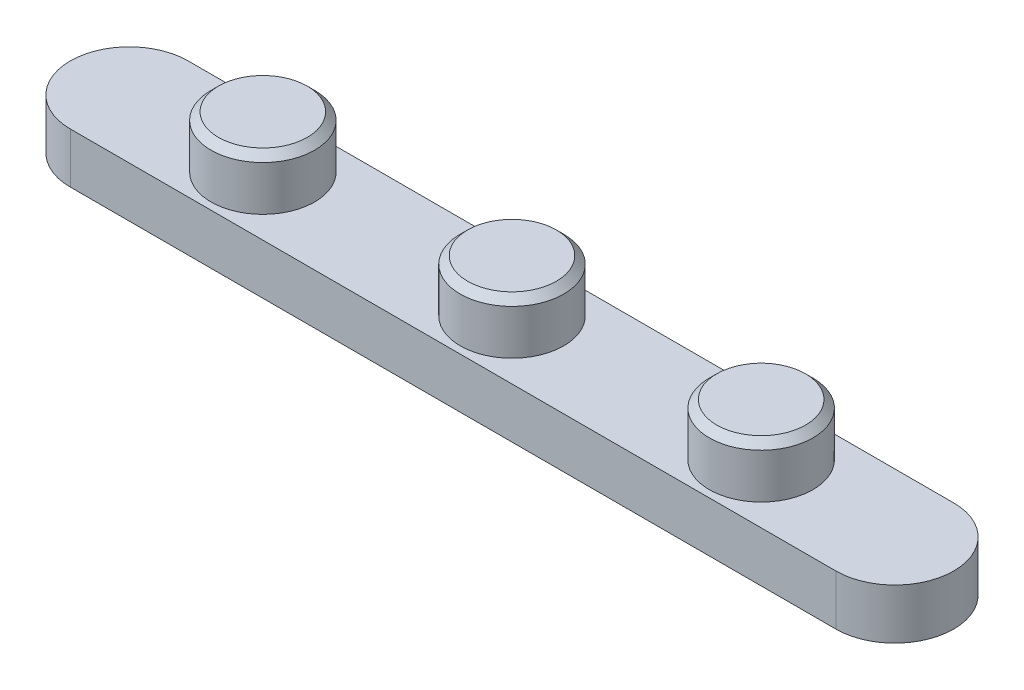
SolidWorks part; units mm, degrees
material "Plain Carbon Steel"
ref_plane "Front Plane" through (0, 0, 0) normal (0, 0, 1) x (1, 0, 0)
ref_plane "Top Plane" through (0, 0, 0) normal (0, 1, 0) x (1, 0, 0)
ref_plane "Right Plane" through (0, 0, 0) normal (1, 0, 0) x (0, 0, -1)
sketch "Sketch1" plane through (0, 0, 0) normal (0, 1, 0) x (1, 0, 0)
  line L0 (-25.855, 0) -> (25.855, 0) construction
  line L1 (-25.855, 3.98) -> (25.855, 3.98)
  line L2 (-25.855, -3.98) -> (25.855, -3.98)
  line L3 (0, 0) -> (0, 65.4823) construction
  arc A0 (-25.855, 3.98) -> (-25.855, -3.98) centre (-25.855, 0) ccw
  arc A1 (25.855, -3.98) -> (25.855, 3.98) centre (25.855, 0) ccw
  circle A2 centre (-16.8275, 0) radius 3.5
  circle A3 centre (0, 0) radius 3.5
  circle A4 centre (16.8275, 0) radius 3.5
  point P2 (0, 0)
  dimension "D1" = 7
  dimension "D4" = 59.67
  dimension "D2" = 7.96
  dimension "D3" = 33.655
extrude "Boss-Extrude1" add sketch "Sketch1" along normal blind 3.4 contours L2 A1 L1 A0
extrude "Boss-Extrude2" add sketch "Sketch1<3>" along normal blind 6.93 contours A2 | A4 region at (-16.8275, 0, 0) region at (16.8275, 0, 0)
sketch "Sketch1<3>" plane through (0, 0, 0) normal (0, 1, 0) x (1, 0, 0) same geometry as "Sketch1"
chamfer "Chamfer1" distance 0.5 angle 45 2 edges at (-16.8275, 6.93, 3.5) (16.8275, 6.93, 3.5)
extrude "Boss-Extrude3" add sketch "Sketch1<4>" along normal blind 6.93 contours A3 region at (0, 0, 0)
sketch "Sketch1<4>" plane through (0, 0, 0) normal (0, 1, 0) x (1, 0, 0) same geometry as "Sketch1"
chamfer "Chamfer2" distance 0.5 angle 45 1 edges at (0, 6.93, 3.5)
